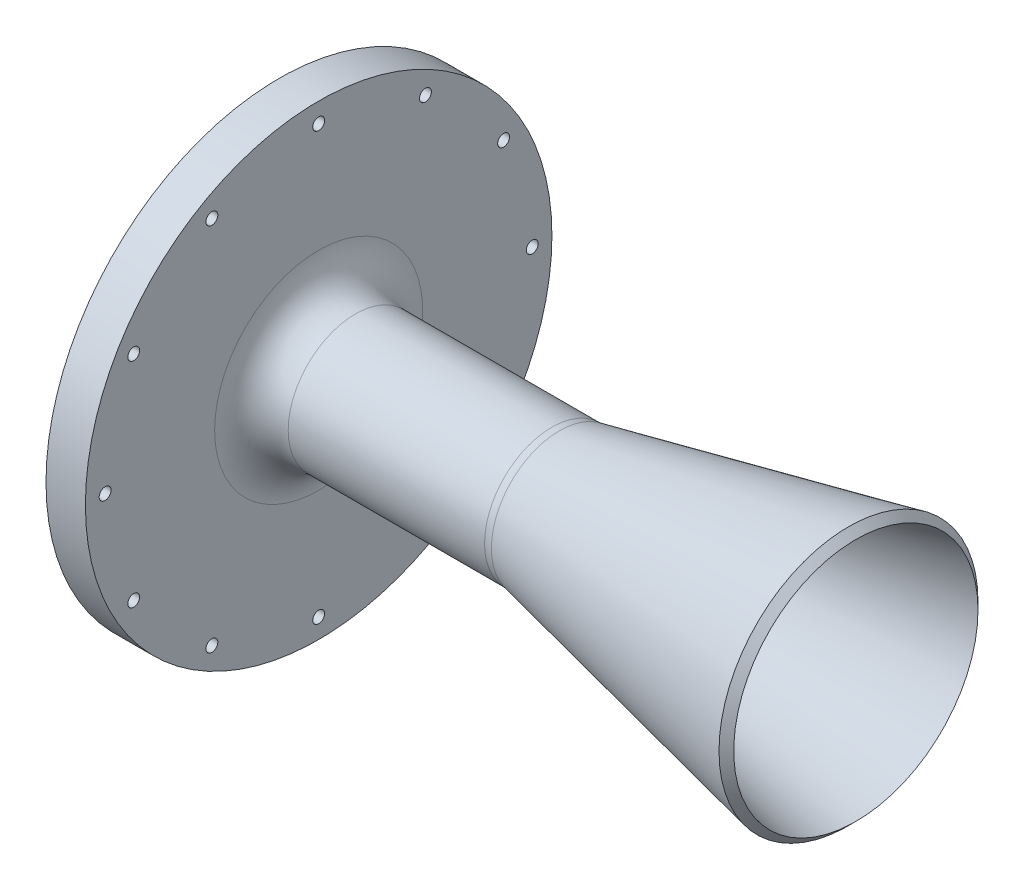
SolidWorks part; units mm, degrees
material "Stainless Steel (ferritic)"
ref_plane "Front Plane" through (0, 0, 0) normal (0, 0, 1) x (1, 0, 0)
ref_plane "Top Plane" through (0, 0, 0) normal (0, 1, 0) x (1, 0, 0)
ref_plane "Right Plane" through (0, 0, 0) normal (1, 0, 0) x (0, 0, -1)
sketch "Sketch2" plane through (0, 0, 0) normal (0, 0, 1) x (1, 0, 0)
  line L0 (0, 0) -> (165.0115, 0) construction
  line L1 (0, 20.5835) -> (0, 56.388)
  line L2 (0, 56.388) -> (9.525, 56.388)
  line L3 (9.525, 56.388) -> (9.525, 16.256)
  line L11 (66.8065, 16.256) -> (139.7, 31.75)
  line L17 (139.7, 31.75) -> (139.7, 29.5925)
  line L18 (60.325, 12.7208) -> (60.325, 14.351)
  line L19 (60.325, 14.351) -> (10.795, 14.351)
  line L20 (0, 20.5835) -> (10.795, 14.351)
  line L21 (60.325, 12.7208) -> (139.7, 29.5925)
  line L22 (9.525, 16.256) -> (66.8065, 16.256)
  dimension "D2" = 9.525
  dimension "D3" = 1.905
  dimension "D4" = 10.795
  dimension "D5" = 14.351
  dimension "D6" = 31.75
  dimension "D7" = 12
  dimension "D8" = 139.7
  dimension "D9" = 1.6302
  dimension "D10" = 30
  dimension "D11" = 56.388
  dimension "D12" = 49.53
revolve "Main Structure" add sketch "Sketch2" angle 360 about L0
sketch "Sketch4" plane through (0, 0, 0) normal (-1, 0, 0) x (0, 0, 1)
  circle A0 centre (0, 0) radius 51.6255 construction
  circle A1 centre (0, -51.6255) radius 2.146
  circle A2 centre (-25.8127, -44.709) radius 2.146
  circle A3 centre (-44.709, -25.8128) radius 2.146
  circle A4 centre (-51.6255, 0) radius 2.146
  circle A5 centre (-44.709, 25.8127) radius 2.146
  circle A6 centre (-25.8128, 44.709) radius 2.146
  circle A7 centre (0, 51.6255) radius 2.146
  circle A8 centre (25.8127, 44.709) radius 2.146
  circle A9 centre (44.709, 25.8128) radius 2.146
  circle A10 centre (51.6255, 0) radius 2.146
  circle A11 centre (44.709, -25.8127) radius 2.146
  circle A12 centre (25.8128, -44.709) radius 2.146
  point P29 (0, 0)
  dimension "D1" = 12
  dimension "D2" = 103.251
hole_wizard "Flange Holes" positions "Sketch7" profile "Sketch8" hole size "#33" standard "ANSI Inch" end condition up to next
sketch "Sketch7" plane through (0, 0, 0) normal (-1, 0, 0) x (0, 0, 1)
  point P0 (0, -51.6255)
  point P3 (-25.8127, -44.709)
  point P6 (-44.709, -25.8128)
  point P9 (-51.6255, 0)
  point P12 (-44.709, 25.8127)
  point P15 (-25.8128, 44.709)
  point P18 (0, 51.6255)
  point P21 (25.8127, 44.709)
  point P24 (44.709, 25.8128)
  point P27 (51.6255, 0)
  point P30 (44.709, -25.8127)
  point P33 (25.8128, -44.709)
sketch "Sketch8" plane through (0, -51.6255, 0) normal (0, 1, 0) x (0, 0, 1)
  line L0 (0, 0) -> (0, 9.525)
  line L1 (0, 9.525) -> (1.4351, 9.525)
  line L2 (1.4351, 9.525) -> (1.4351, 0)
  line L5 (1.4351, 0) -> (0, 0)
  line L11 (0, -6.35) -> (0, 107.95) construction
  dimension "Thru Hole Dia." = 2.8702
  dimension "Thru Hole Depth" = 9.525
sketch "Sketch9" plane through (0, 0, 0) normal (-1, 0, 0) x (0, 0, 1)
  line L0 (0, 0) -> (-67.6727, 18.1329) construction
  line L1 (0, 0) -> (-51.6255, 0) construction
  circle A0 centre (0, 0) radius 51.6255 construction
  circle A1 centre (-49.8664, 13.3617) radius 2.9451
  circle A2 centre (49.8664, -13.3617) radius 2.9451
  point P14 (0, 0)
  dimension "D1" = 15
  dimension "D2" = 2
hole_wizard "Dowel Holes" positions "Sketch10" profile "Sketch11" hole size "3/16" standard "ANSI Inch"
sketch "Sketch10" plane through (0, 0, 0) normal (-1, 0, 0) x (0, 0, 1)
  point P0 (49.8664, -13.3617)
  point P3 (-49.8664, 13.3617)
sketch "Sketch11" plane through (0, -13.3617, 49.8664) normal (0, 1, 0) x (0, 0, 1)
  line L0 (0, 0) -> (0, 7.7808)
  line L1 (0, 7.7808) -> (2.3812, 6.35)
  line L2 (2.3812, 6.35) -> (2.3812, 0)
  line L5 (2.3812, 0) -> (0, 0)
  line L10 (0, 7.7808) -> (-2.3812, 6.35) construction
  line L11 (0, -6.35) -> (0, 107.95) construction
  dimension "Hole Dia." = 4.7625
  dimension "Hole Depth" = 6.35
  dimension "Drill Angle" = 118
fillet "Fillet1" radius 8.89 2 edges at (66.8065, 0, 16.256) (9.525, 0, 16.256)
sketch "Sketch13" plane through (0, 0, 0) normal (0, 1, 0) x (1, 0, 0)
  line L0 (0, 38.1) -> (3.3333, 0)
  line L1 (0, 56.388) -> (0, -56.388) construction
  line L2 (3.3333, 0) -> (0, 0)
  line L3 (0, 0) -> (0, 38.1)
  dimension "D1" = 38.1
  dimension "D2" = 5
revolve "Cut-Revolve1" cut sketch "Sketch13" angle 360 about L2
chamfer "Chamfer1" distance 2.54 angle 45 1 edges at (139.7, 0, 31.75) first distance on face at (139.7, 0, 31.75)
